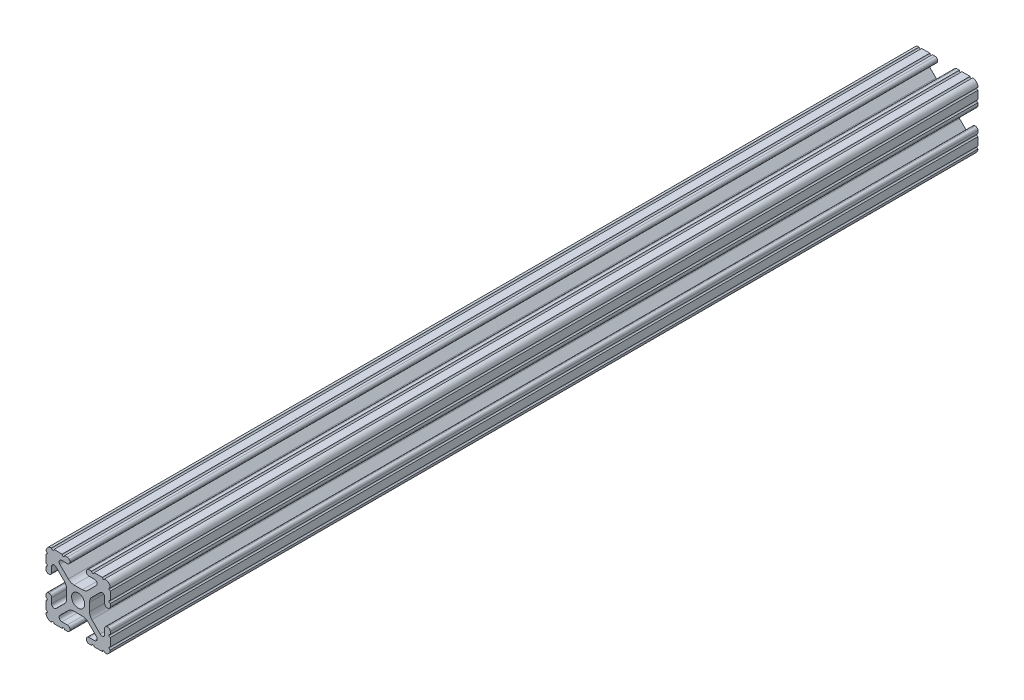
SolidWorks part; units mm, degrees
ref_plane "Front Plane" through (0, 0, 0) normal (0, 0, 1) x (1, 0, 0)
ref_plane "Top Plane" through (0, 0, 0) normal (0, 1, 0) x (1, 0, 0)
ref_plane "Right Plane" through (0, 0, 0) normal (1, 0, 0) x (0, 0, -1)
sketch "Sketch1" plane through (0, 0, 0) normal (0, 0, 1) x (1, 0, 0)
  line L88 (-7.1797, -8.6452) -> (-3.9523, -5.4237)
  line L89 (-1.7093, -4.4958) -> (1.7093, -4.4958)
  line L90 (3.9523, -5.4237) -> (7.1797, -8.6452)
  line L91 (6.4164, -10.4902) -> (4.2875, -10.4902)
  line L92 (3.2385, -11.5392) -> (3.2385, -11.651)
  line L93 (4.2875, -12.7) -> (5.3171, -12.7)
  line L94 (6.3331, -12.7) -> (9.5504, -12.7)
  line L95 (12.7, -9.5504) -> (12.7, -6.3331)
  line L96 (12.7, -5.3171) -> (12.7, -4.2875)
  line L97 (11.651, -3.2385) -> (11.5392, -3.2385)
  line L98 (10.4902, -4.2875) -> (10.4902, -6.4021)
  line L99 (8.7371, -7.1294) -> (5.441, -3.8408)
  line L100 (4.5085, -1.5932) -> (4.5085, 1.5932)
  line L101 (5.441, 3.8408) -> (8.7371, 7.1294)
  line L102 (10.4902, 6.4021) -> (10.4902, 4.2875)
  line L103 (11.5392, 3.2385) -> (11.651, 3.2385)
  line L104 (12.7, 4.2875) -> (12.7, 5.3171)
  line L105 (12.7, 6.3331) -> (12.7, 9.5504)
  line L106 (9.5504, 12.7) -> (6.3331, 12.7)
  line L107 (5.3171, 12.7) -> (4.2875, 12.7)
  line L108 (3.2385, 11.651) -> (3.2385, 11.5392)
  line L109 (4.2875, 10.4902) -> (6.4768, 10.4902)
  line L110 (7.207, 8.7244) -> (3.8983, 5.4232)
  line L111 (1.6558, 4.4958) -> (-1.6558, 4.4958)
  line L112 (-3.8983, 5.4232) -> (-7.207, 8.7244)
  line L113 (-6.4768, 10.4902) -> (-4.2875, 10.4902)
  line L114 (-3.2385, 11.5392) -> (-3.2385, 11.651)
  line L115 (-4.2875, 12.7) -> (-5.3171, 12.7)
  line L116 (-6.3331, 12.7) -> (-9.5504, 12.7)
  line L117 (-12.7, 9.5504) -> (-12.7, 6.3331)
  line L118 (-12.7, 5.3171) -> (-12.7, 4.2875)
  line L119 (-11.651, 3.2385) -> (-11.5392, 3.2385)
  line L120 (-10.4902, 4.2875) -> (-10.4902, 6.4021)
  line L121 (-8.7371, 7.1294) -> (-5.441, 3.8408)
  line L122 (-4.5085, 1.5932) -> (-4.5085, -1.5932)
  line L123 (-5.441, -3.8408) -> (-8.7371, -7.1294)
  line L124 (-10.4902, -6.4021) -> (-10.4902, -4.2875)
  line L125 (-11.5392, -3.2385) -> (-11.651, -3.2385)
  line L126 (-12.7, -4.2875) -> (-12.7, -5.3171)
  line L127 (-12.7, -6.3331) -> (-12.7, -9.5504)
  line L128 (-9.5504, -12.7) -> (-6.3331, -12.7)
  line L129 (-5.3171, -12.7) -> (-4.2875, -12.7)
  line L130 (-3.2385, -11.651) -> (-3.2385, -11.5392)
  line L131 (-4.2875, -10.4902) -> (-6.4164, -10.4902)
  circle A1 centre (0, 0) radius 2.6035
  arc A104 (-7.1797, -8.6452) -> (-6.4164, -10.4902) centre (-6.4164, -9.4098) ccw
  arc A105 (-1.7093, -4.4958) -> (-3.9523, -5.4237) centre (-1.7093, -7.6708) ccw
  arc A106 (3.9523, -5.4237) -> (1.7093, -4.4958) centre (1.7093, -7.6708) ccw
  arc A107 (6.4164, -10.4902) -> (7.1797, -8.6452) centre (6.4164, -9.4098) ccw
  arc A108 (4.2875, -10.4902) -> (3.2385, -11.5392) centre (4.2875, -11.5392) ccw
  arc A109 (3.2385, -11.651) -> (4.2875, -12.7) centre (4.2875, -11.651) ccw
  arc A110 (6.3331, -12.7) -> (5.3171, -12.7) centre (5.8251, -12.7) ccw
  arc A111 (10.5664, -12.6998) -> (9.5504, -12.7) centre (10.0584, -12.7) ccw
  arc A112 (10.5664, -12.6998) -> (12.6998, -10.5664) centre (10.5918, -10.5918) ccw
  arc A113 (12.7, -9.5504) -> (12.6998, -10.5664) centre (12.7, -10.0584) ccw
  arc A114 (12.7, -5.3171) -> (12.7, -6.3331) centre (12.7, -5.8251) ccw
  arc A115 (12.7, -4.2875) -> (11.651, -3.2385) centre (11.651, -4.2875) ccw
  arc A116 (11.5392, -3.2385) -> (10.4902, -4.2875) centre (11.5392, -4.2875) ccw
  arc A117 (8.7371, -7.1294) -> (10.4902, -6.4021) centre (9.4628, -6.4021) ccw
  arc A118 (4.5085, -1.5932) -> (5.441, -3.8408) centre (7.6835, -1.5932) ccw
  arc A119 (5.441, 3.8408) -> (4.5085, 1.5932) centre (7.6835, 1.5932) ccw
  arc A120 (10.4902, 6.4021) -> (8.7371, 7.1294) centre (9.4628, 6.4021) ccw
  arc A121 (10.4902, 4.2875) -> (11.5392, 3.2385) centre (11.5392, 4.2875) ccw
  arc A122 (11.651, 3.2385) -> (12.7, 4.2875) centre (11.651, 4.2875) ccw
  arc A123 (12.7, 6.3331) -> (12.7, 5.3171) centre (12.7, 5.8251) ccw
  arc A124 (12.6998, 10.5664) -> (12.7, 9.5504) centre (12.7, 10.0584) ccw
  arc A125 (12.6998, 10.5664) -> (10.5664, 12.6998) centre (10.5918, 10.5918) ccw
  arc A126 (9.5504, 12.7) -> (10.5664, 12.6998) centre (10.0584, 12.7) ccw
  arc A127 (5.3171, 12.7) -> (6.3331, 12.7) centre (5.8251, 12.7) ccw
  arc A128 (4.2875, 12.7) -> (3.2385, 11.651) centre (4.2875, 11.651) ccw
  arc A129 (3.2385, 11.5392) -> (4.2875, 10.4902) centre (4.2875, 11.5392) ccw
  arc A130 (7.207, 8.7244) -> (6.4768, 10.4902) centre (6.4768, 9.4563) ccw
  arc A131 (1.6558, 4.4958) -> (3.8983, 5.4232) centre (1.6558, 7.6708) ccw
  arc A132 (-3.8983, 5.4232) -> (-1.6558, 4.4958) centre (-1.6558, 7.6708) ccw
  arc A133 (-6.4768, 10.4902) -> (-7.207, 8.7244) centre (-6.4768, 9.4563) ccw
  arc A134 (-4.2875, 10.4902) -> (-3.2385, 11.5392) centre (-4.2875, 11.5392) ccw
  arc A135 (-3.2385, 11.651) -> (-4.2875, 12.7) centre (-4.2875, 11.651) ccw
  arc A136 (-6.3331, 12.7) -> (-5.3171, 12.7) centre (-5.8251, 12.7) ccw
  arc A137 (-10.5664, 12.6998) -> (-9.5504, 12.7) centre (-10.0584, 12.7) ccw
  arc A138 (-10.5664, 12.6998) -> (-12.6998, 10.5664) centre (-10.5918, 10.5918) ccw
  arc A139 (-12.7, 9.5504) -> (-12.6998, 10.5664) centre (-12.7, 10.0584) ccw
  arc A140 (-12.7, 5.3171) -> (-12.7, 6.3331) centre (-12.7, 5.8251) ccw
  arc A141 (-12.7, 4.2875) -> (-11.651, 3.2385) centre (-11.651, 4.2875) ccw
  arc A142 (-11.5392, 3.2385) -> (-10.4902, 4.2875) centre (-11.5392, 4.2875) ccw
  arc A143 (-8.7371, 7.1294) -> (-10.4902, 6.4021) centre (-9.4628, 6.4021) ccw
  arc A144 (-4.5085, 1.5932) -> (-5.441, 3.8408) centre (-7.6835, 1.5932) ccw
  arc A145 (-5.441, -3.8408) -> (-4.5085, -1.5932) centre (-7.6835, -1.5932) ccw
  arc A146 (-10.4902, -6.4021) -> (-8.7371, -7.1294) centre (-9.4628, -6.4021) ccw
  arc A147 (-10.4902, -4.2875) -> (-11.5392, -3.2385) centre (-11.5392, -4.2875) ccw
  arc A148 (-11.651, -3.2385) -> (-12.7, -4.2875) centre (-11.651, -4.2875) ccw
  arc A149 (-12.7, -6.3331) -> (-12.7, -5.3171) centre (-12.7, -5.8251) ccw
  arc A150 (-12.6998, -10.5664) -> (-12.7, -9.5504) centre (-12.7, -10.0584) ccw
  arc A151 (-12.6998, -10.5664) -> (-10.5664, -12.6998) centre (-10.5918, -10.5918) ccw
  arc A152 (-9.5504, -12.7) -> (-10.5664, -12.6998) centre (-10.0584, -12.7) ccw
  arc A153 (-5.3171, -12.7) -> (-6.3331, -12.7) centre (-5.8251, -12.7) ccw
  arc A154 (-4.2875, -12.7) -> (-3.2385, -11.651) centre (-4.2875, -11.651) ccw
  arc A155 (-3.2385, -11.5392) -> (-4.2875, -10.4902) centre (-4.2875, -11.5392) ccw
extrude "Boss-Extrude1" add sketch "Sketch1" along normal mid plane 431.8
ref_plane "Plane1" through (0, 0, 0) normal (0, 1, 0) x (1, 0, 0)
ref_plane "Plane2" through (0, 0, 0) normal (-1, 0, 0) x (0, 0, 1)
sketch "Sketch2" plane through (0, 0, -215.9) normal (0, 0, -1) x (-1, 0, 0)
  line L44 (6.4164, -10.4902) -> (4.2875, -10.4902)
  line L45 (3.2385, -11.5392) -> (3.2385, -11.651)
  line L46 (4.2875, -12.7) -> (5.3171, -12.7)
  line L47 (6.3331, -12.7) -> (9.5504, -12.7)
  line L48 (12.7, -9.5504) -> (12.7, -6.3331)
  line L49 (12.7, -5.3171) -> (12.7, -4.2875)
  line L50 (11.651, -3.2385) -> (11.5392, -3.2385)
  line L51 (10.4902, -4.2875) -> (10.4902, -6.4021)
  line L52 (8.7371, -7.1294) -> (5.441, -3.8408)
  line L53 (4.5085, -1.5932) -> (4.5085, 1.5932)
  line L54 (5.441, 3.8408) -> (8.7371, 7.1294)
  line L55 (10.4902, 6.4021) -> (10.4902, 4.2875)
  line L56 (11.5392, 3.2385) -> (11.651, 3.2385)
  line L57 (12.7, 4.2875) -> (12.7, 5.3171)
  line L58 (12.7, 6.3331) -> (12.7, 9.5504)
  line L59 (9.5504, 12.7) -> (6.3331, 12.7)
  line L60 (5.3171, 12.7) -> (4.2875, 12.7)
  line L61 (3.2385, 11.651) -> (3.2385, 11.5392)
  line L62 (4.2875, 10.4902) -> (6.4768, 10.4902)
  line L63 (7.207, 8.7244) -> (3.8983, 5.4232)
  line L64 (1.6558, 4.4958) -> (-1.6558, 4.4958)
  line L65 (-3.8983, 5.4232) -> (-7.207, 8.7244)
  line L66 (-6.4768, 10.4902) -> (-4.2875, 10.4902)
  line L67 (-3.2385, 11.5392) -> (-3.2385, 11.651)
  line L68 (-4.2875, 12.7) -> (-5.3171, 12.7)
  line L69 (-6.3331, 12.7) -> (-9.5504, 12.7)
  line L70 (-12.7, 9.5504) -> (-12.7, 6.3331)
  line L71 (-12.7, 5.3171) -> (-12.7, 4.2875)
  line L72 (-11.651, 3.2385) -> (-11.5392, 3.2385)
  line L73 (-10.4902, 4.2875) -> (-10.4902, 6.4021)
  line L74 (-8.7371, 7.1294) -> (-5.441, 3.8408)
  line L75 (-4.5085, 1.5932) -> (-4.5085, -1.5932)
  line L76 (-5.441, -3.8408) -> (-8.7371, -7.1294)
  line L77 (-10.4902, -6.4021) -> (-10.4902, -4.2875)
  line L78 (-11.5392, -3.2385) -> (-11.651, -3.2385)
  line L79 (-12.7, -4.2875) -> (-12.7, -5.3171)
  line L80 (-12.7, -6.3331) -> (-12.7, -9.5504)
  line L81 (-9.5504, -12.7) -> (-6.3331, -12.7)
  line L82 (-5.3171, -12.7) -> (-4.2875, -12.7)
  line L83 (-3.2385, -11.651) -> (-3.2385, -11.5392)
  line L84 (-4.2875, -10.4902) -> (-6.4164, -10.4902)
  line L85 (-7.1797, -8.6452) -> (-3.9523, -5.4237)
  line L86 (-1.7093, -4.4958) -> (1.7093, -4.4958)
  line L87 (3.9523, -5.4237) -> (7.1797, -8.6452)
  line L88 (6.4164, -10.4902) -> (4.2875, -10.4902)
  line L89 (3.2385, -11.5392) -> (3.2385, -11.651)
  line L90 (4.2875, -12.7) -> (5.3171, -12.7)
  line L91 (6.3331, -12.7) -> (9.5504, -12.7)
  line L92 (12.7, -9.5504) -> (12.7, -6.3331)
  line L93 (12.7, -5.3171) -> (12.7, -4.2875)
  line L94 (11.651, -3.2385) -> (11.5392, -3.2385)
  line L95 (10.4902, -4.2875) -> (10.4902, -6.4021)
  line L96 (8.7371, -7.1294) -> (5.441, -3.8408)
  line L97 (4.5085, -1.5932) -> (4.5085, 1.5932)
  line L98 (5.441, 3.8408) -> (8.7371, 7.1294)
  line L99 (10.4902, 6.4021) -> (10.4902, 4.2875)
  line L100 (11.5392, 3.2385) -> (11.651, 3.2385)
  line L101 (12.7, 4.2875) -> (12.7, 5.3171)
  line L102 (12.7, 6.3331) -> (12.7, 9.5504)
  line L103 (9.5504, 12.7) -> (6.3331, 12.7)
  line L104 (5.3171, 12.7) -> (4.2875, 12.7)
  line L105 (3.2385, 11.651) -> (3.2385, 11.5392)
  line L106 (4.2875, 10.4902) -> (6.4768, 10.4902)
  line L107 (7.207, 8.7244) -> (3.8983, 5.4232)
  line L108 (1.6558, 4.4958) -> (-1.6558, 4.4958)
  line L109 (-3.8983, 5.4232) -> (-7.207, 8.7244)
  line L110 (-6.4768, 10.4902) -> (-4.2875, 10.4902)
  line L111 (-3.2385, 11.5392) -> (-3.2385, 11.651)
  line L112 (-4.2875, 12.7) -> (-5.3171, 12.7)
  line L113 (-6.3331, 12.7) -> (-9.5504, 12.7)
  line L114 (-12.7, 9.5504) -> (-12.7, 6.3331)
  line L115 (-12.7, 5.3171) -> (-12.7, 4.2875)
  line L116 (-11.651, 3.2385) -> (-11.5392, 3.2385)
  line L117 (-10.4902, 4.2875) -> (-10.4902, 6.4021)
  line L118 (-8.7371, 7.1294) -> (-5.441, 3.8408)
  line L119 (-4.5085, 1.5932) -> (-4.5085, -1.5932)
  line L120 (-5.441, -3.8408) -> (-8.7371, -7.1294)
  line L121 (-10.4902, -6.4021) -> (-10.4902, -4.2875)
  line L122 (-11.5392, -3.2385) -> (-11.651, -3.2385)
  line L123 (-12.7, -4.2875) -> (-12.7, -5.3171)
  line L124 (-12.7, -6.3331) -> (-12.7, -9.5504)
  line L125 (-9.5504, -12.7) -> (-6.3331, -12.7)
  line L126 (-5.3171, -12.7) -> (-4.2875, -12.7)
  line L127 (-3.2385, -11.651) -> (-3.2385, -11.5392)
  line L128 (-4.2875, -10.4902) -> (-6.4164, -10.4902)
  line L129 (-7.1797, -8.6452) -> (-3.9523, -5.4237)
  line L130 (-1.7093, -4.4958) -> (1.7093, -4.4958)
  line L131 (3.9523, -5.4237) -> (7.1797, -8.6452)
  arc A52 (6.4164, -10.4902) -> (7.1797, -8.6452) centre (6.4164, -9.4098) ccw
  arc A53 (4.2875, -10.4902) -> (3.2385, -11.5392) centre (4.2875, -11.5392) ccw
  arc A54 (3.2385, -11.651) -> (4.2875, -12.7) centre (4.2875, -11.651) ccw
  arc A55 (6.3331, -12.7) -> (5.3171, -12.7) centre (5.8251, -12.7) ccw
  arc A56 (10.5664, -12.6998) -> (9.5504, -12.7) centre (10.0584, -12.7) ccw
  arc A57 (10.5664, -12.6998) -> (12.6998, -10.5664) centre (10.5918, -10.5918) ccw
  arc A58 (12.7, -9.5504) -> (12.6998, -10.5664) centre (12.7, -10.0584) ccw
  arc A59 (12.7, -5.3171) -> (12.7, -6.3331) centre (12.7, -5.8251) ccw
  arc A60 (12.7, -4.2875) -> (11.651, -3.2385) centre (11.651, -4.2875) ccw
  arc A61 (11.5392, -3.2385) -> (10.4902, -4.2875) centre (11.5392, -4.2875) ccw
  arc A62 (8.7371, -7.1294) -> (10.4902, -6.4021) centre (9.4628, -6.4021) ccw
  arc A63 (4.5085, -1.5932) -> (5.441, -3.8408) centre (7.6835, -1.5932) ccw
  arc A64 (5.441, 3.8408) -> (4.5085, 1.5932) centre (7.6835, 1.5932) ccw
  arc A65 (10.4902, 6.4021) -> (8.7371, 7.1294) centre (9.4628, 6.4021) ccw
  arc A66 (10.4902, 4.2875) -> (11.5392, 3.2385) centre (11.5392, 4.2875) ccw
  arc A67 (11.651, 3.2385) -> (12.7, 4.2875) centre (11.651, 4.2875) ccw
  arc A68 (12.7, 6.3331) -> (12.7, 5.3171) centre (12.7, 5.8251) ccw
  arc A69 (12.6998, 10.5664) -> (12.7, 9.5504) centre (12.7, 10.0584) ccw
  arc A70 (12.6998, 10.5664) -> (10.5664, 12.6998) centre (10.5918, 10.5918) ccw
  arc A71 (9.5504, 12.7) -> (10.5664, 12.6998) centre (10.0584, 12.7) ccw
  arc A72 (5.3171, 12.7) -> (6.3331, 12.7) centre (5.8251, 12.7) ccw
  arc A73 (4.2875, 12.7) -> (3.2385, 11.651) centre (4.2875, 11.651) ccw
  arc A74 (3.2385, 11.5392) -> (4.2875, 10.4902) centre (4.2875, 11.5392) ccw
  arc A75 (7.207, 8.7244) -> (6.4768, 10.4902) centre (6.4768, 9.4563) ccw
  arc A76 (1.6558, 4.4958) -> (3.8983, 5.4232) centre (1.6558, 7.6708) ccw
  arc A77 (-3.8983, 5.4232) -> (-1.6558, 4.4958) centre (-1.6558, 7.6708) ccw
  arc A78 (-6.4768, 10.4902) -> (-7.207, 8.7244) centre (-6.4768, 9.4563) ccw
  arc A79 (-4.2875, 10.4902) -> (-3.2385, 11.5392) centre (-4.2875, 11.5392) ccw
  arc A80 (-3.2385, 11.651) -> (-4.2875, 12.7) centre (-4.2875, 11.651) ccw
  arc A81 (-6.3331, 12.7) -> (-5.3171, 12.7) centre (-5.8251, 12.7) ccw
  arc A82 (-10.5664, 12.6998) -> (-9.5504, 12.7) centre (-10.0584, 12.7) ccw
  arc A83 (-10.5664, 12.6998) -> (-12.6998, 10.5664) centre (-10.5918, 10.5918) ccw
  arc A84 (-12.7, 9.5504) -> (-12.6998, 10.5664) centre (-12.7, 10.0584) ccw
  arc A85 (-12.7, 5.3171) -> (-12.7, 6.3331) centre (-12.7, 5.8251) ccw
  arc A86 (-12.7, 4.2875) -> (-11.651, 3.2385) centre (-11.651, 4.2875) ccw
  arc A87 (-11.5392, 3.2385) -> (-10.4902, 4.2875) centre (-11.5392, 4.2875) ccw
  arc A88 (-8.7371, 7.1294) -> (-10.4902, 6.4021) centre (-9.4628, 6.4021) ccw
  arc A89 (-4.5085, 1.5932) -> (-5.441, 3.8408) centre (-7.6835, 1.5932) ccw
  arc A90 (-5.441, -3.8408) -> (-4.5085, -1.5932) centre (-7.6835, -1.5932) ccw
  arc A91 (-10.4902, -6.4021) -> (-8.7371, -7.1294) centre (-9.4628, -6.4021) ccw
  arc A92 (-10.4902, -4.2875) -> (-11.5392, -3.2385) centre (-11.5392, -4.2875) ccw
  arc A93 (-11.651, -3.2385) -> (-12.7, -4.2875) centre (-11.651, -4.2875) ccw
  arc A94 (-12.7, -6.3331) -> (-12.7, -5.3171) centre (-12.7, -5.8251) ccw
  arc A95 (-12.6998, -10.5664) -> (-12.7, -9.5504) centre (-12.7, -10.0584) ccw
  arc A96 (-12.6998, -10.5664) -> (-10.5664, -12.6998) centre (-10.5918, -10.5918) ccw
  arc A97 (-9.5504, -12.7) -> (-10.5664, -12.6998) centre (-10.0584, -12.7) ccw
  arc A98 (-5.3171, -12.7) -> (-6.3331, -12.7) centre (-5.8251, -12.7) ccw
  arc A99 (-4.2875, -12.7) -> (-3.2385, -11.651) centre (-4.2875, -11.651) ccw
  arc A100 (-3.2385, -11.5392) -> (-4.2875, -10.4902) centre (-4.2875, -11.5392) ccw
  arc A101 (-7.1797, -8.6452) -> (-6.4164, -10.4902) centre (-6.4164, -9.4098) ccw
  arc A102 (-1.7093, -4.4958) -> (-3.9523, -5.4237) centre (-1.7093, -7.6708) ccw
  arc A103 (3.9523, -5.4237) -> (1.7093, -4.4958) centre (1.7093, -7.6708) ccw
  arc A104 (6.4164, -10.4902) -> (7.1797, -8.6452) centre (6.4164, -9.4098) ccw
  arc A105 (4.2875, -10.4902) -> (3.2385, -11.5392) centre (4.2875, -11.5392) ccw
  arc A106 (3.2385, -11.651) -> (4.2875, -12.7) centre (4.2875, -11.651) ccw
  arc A107 (6.3331, -12.7) -> (5.3171, -12.7) centre (5.8251, -12.7) ccw
  arc A108 (10.5664, -12.6998) -> (9.5504, -12.7) centre (10.0584, -12.7) ccw
  arc A109 (10.5664, -12.6998) -> (12.6998, -10.5664) centre (10.5918, -10.5918) ccw
  arc A110 (12.7, -9.5504) -> (12.6998, -10.5664) centre (12.7, -10.0584) ccw
  arc A111 (12.7, -5.3171) -> (12.7, -6.3331) centre (12.7, -5.8251) ccw
  arc A112 (12.7, -4.2875) -> (11.651, -3.2385) centre (11.651, -4.2875) ccw
  arc A113 (11.5392, -3.2385) -> (10.4902, -4.2875) centre (11.5392, -4.2875) ccw
  arc A114 (8.7371, -7.1294) -> (10.4902, -6.4021) centre (9.4628, -6.4021) ccw
  arc A115 (4.5085, -1.5932) -> (5.441, -3.8408) centre (7.6835, -1.5932) ccw
  arc A116 (5.441, 3.8408) -> (4.5085, 1.5932) centre (7.6835, 1.5932) ccw
  arc A117 (10.4902, 6.4021) -> (8.7371, 7.1294) centre (9.4628, 6.4021) ccw
  arc A118 (10.4902, 4.2875) -> (11.5392, 3.2385) centre (11.5392, 4.2875) ccw
  arc A119 (11.651, 3.2385) -> (12.7, 4.2875) centre (11.651, 4.2875) ccw
  arc A120 (12.7, 6.3331) -> (12.7, 5.3171) centre (12.7, 5.8251) ccw
  arc A121 (12.6998, 10.5664) -> (12.7, 9.5504) centre (12.7, 10.0584) ccw
  arc A122 (12.6998, 10.5664) -> (10.5664, 12.6998) centre (10.5918, 10.5918) ccw
  arc A123 (9.5504, 12.7) -> (10.5664, 12.6998) centre (10.0584, 12.7) ccw
  arc A124 (5.3171, 12.7) -> (6.3331, 12.7) centre (5.8251, 12.7) ccw
  arc A125 (4.2875, 12.7) -> (3.2385, 11.651) centre (4.2875, 11.651) ccw
  arc A126 (3.2385, 11.5392) -> (4.2875, 10.4902) centre (4.2875, 11.5392) ccw
  arc A127 (7.207, 8.7244) -> (6.4768, 10.4902) centre (6.4768, 9.4563) ccw
  arc A128 (1.6558, 4.4958) -> (3.8983, 5.4232) centre (1.6558, 7.6708) ccw
  arc A129 (-3.8983, 5.4232) -> (-1.6558, 4.4958) centre (-1.6558, 7.6708) ccw
  arc A130 (-6.4768, 10.4902) -> (-7.207, 8.7244) centre (-6.4768, 9.4563) ccw
  arc A131 (-4.2875, 10.4902) -> (-3.2385, 11.5392) centre (-4.2875, 11.5392) ccw
  arc A132 (-3.2385, 11.651) -> (-4.2875, 12.7) centre (-4.2875, 11.651) ccw
  arc A133 (-6.3331, 12.7) -> (-5.3171, 12.7) centre (-5.8251, 12.7) ccw
  arc A134 (-10.5664, 12.6998) -> (-9.5504, 12.7) centre (-10.0584, 12.7) ccw
  arc A135 (-10.5664, 12.6998) -> (-12.6998, 10.5664) centre (-10.5918, 10.5918) ccw
  arc A136 (-12.7, 9.5504) -> (-12.6998, 10.5664) centre (-12.7, 10.0584) ccw
  arc A137 (-12.7, 5.3171) -> (-12.7, 6.3331) centre (-12.7, 5.8251) ccw
  arc A138 (-12.7, 4.2875) -> (-11.651, 3.2385) centre (-11.651, 4.2875) ccw
  arc A139 (-11.5392, 3.2385) -> (-10.4902, 4.2875) centre (-11.5392, 4.2875) ccw
  arc A140 (-8.7371, 7.1294) -> (-10.4902, 6.4021) centre (-9.4628, 6.4021) ccw
  arc A141 (-4.5085, 1.5932) -> (-5.441, 3.8408) centre (-7.6835, 1.5932) ccw
  arc A142 (-5.441, -3.8408) -> (-4.5085, -1.5932) centre (-7.6835, -1.5932) ccw
  arc A143 (-10.4902, -6.4021) -> (-8.7371, -7.1294) centre (-9.4628, -6.4021) ccw
  arc A144 (-10.4902, -4.2875) -> (-11.5392, -3.2385) centre (-11.5392, -4.2875) ccw
  arc A145 (-11.651, -3.2385) -> (-12.7, -4.2875) centre (-11.651, -4.2875) ccw
  arc A146 (-12.7, -6.3331) -> (-12.7, -5.3171) centre (-12.7, -5.8251) ccw
  arc A147 (-12.6998, -10.5664) -> (-12.7, -9.5504) centre (-12.7, -10.0584) ccw
  arc A148 (-12.6998, -10.5664) -> (-10.5664, -12.6998) centre (-10.5918, -10.5918) ccw
  arc A149 (-9.5504, -12.7) -> (-10.5664, -12.6998) centre (-10.0584, -12.7) ccw
  arc A150 (-5.3171, -12.7) -> (-6.3331, -12.7) centre (-5.8251, -12.7) ccw
  arc A151 (-4.2875, -12.7) -> (-3.2385, -11.651) centre (-4.2875, -11.651) ccw
  arc A152 (-3.2385, -11.5392) -> (-4.2875, -10.4902) centre (-4.2875, -11.5392) ccw
  arc A153 (-7.1797, -8.6452) -> (-6.4164, -10.4902) centre (-6.4164, -9.4098) ccw
  arc A154 (-1.7093, -4.4958) -> (-3.9523, -5.4237) centre (-1.7093, -7.6708) ccw
  arc A155 (3.9523, -5.4237) -> (1.7093, -4.4958) centre (1.7093, -7.6708) ccw
  dimension "D1" = 0
extrude "Cut-Extrude1" cut sketch "Sketch2" against normal up to surface (88.9 mm away)
sketch "Sketch3" plane through (0, 12.7, 0) normal (0, 1, 0) x (1, 0, 0)
  circle A1 centre (0, -44.45) radius 3.175 construction
  circle A2 centre (0, -165.1) radius 3.175 construction
  circle A3 centre (0, 76.2) radius 3.175 construction
  circle A5 centre (0, -44.45) radius 3.175
  circle A6 centre (0, -165.1) radius 3.175
  circle A7 centre (0, 76.2) radius 3.175
extrude "Cut-Extrude2" cut sketch "Sketch3" against normal through all
sketch "Sketch4" plane through (0, -12.7, 0) normal (0, -1, 0) x (1, 0, 0)
  line L4 (-9.5504, 215.9) -> (-9.5504, -127)
  line L5 (-9.5504, -127) -> (-6.3331, -127)
  line L6 (-6.3331, -127) -> (-6.3331, 215.9)
  line L7 (-6.3331, 215.9) -> (-9.5504, 215.9)
  line L8 (-9.5504, 215.9) -> (-9.5504, -127) construction
  line L9 (-9.5504, -127) -> (-6.3331, -127) construction
  line L10 (-6.3331, -127) -> (-6.3331, 215.9) construction
  line L11 (-6.3331, 215.9) -> (-9.5504, 215.9) construction
  circle A0 centre (0, 165.1) radius 3.175 construction
  circle A1 centre (0, 44.45) radius 3.175 construction
  circle A2 centre (0, -76.2) radius 3.175 construction
  circle A3 centre (0, 165.1) radius 3.175 construction
  circle A4 centre (0, 44.45) radius 3.175 construction
  circle A5 centre (0, -76.2) radius 3.175 construction
  circle A6 centre (0, -76.2) radius 4.7625
  circle A7 centre (0, 44.45) radius 4.7625
  circle A8 centre (0.4613, 164.4892) radius 4.7625
  dimension "D2" = 9.525
  dimension "D1" = 0
extrude "Cut-Extrude3" cut sketch "Sketch4" against normal up to vertex (8.2042 mm away)
